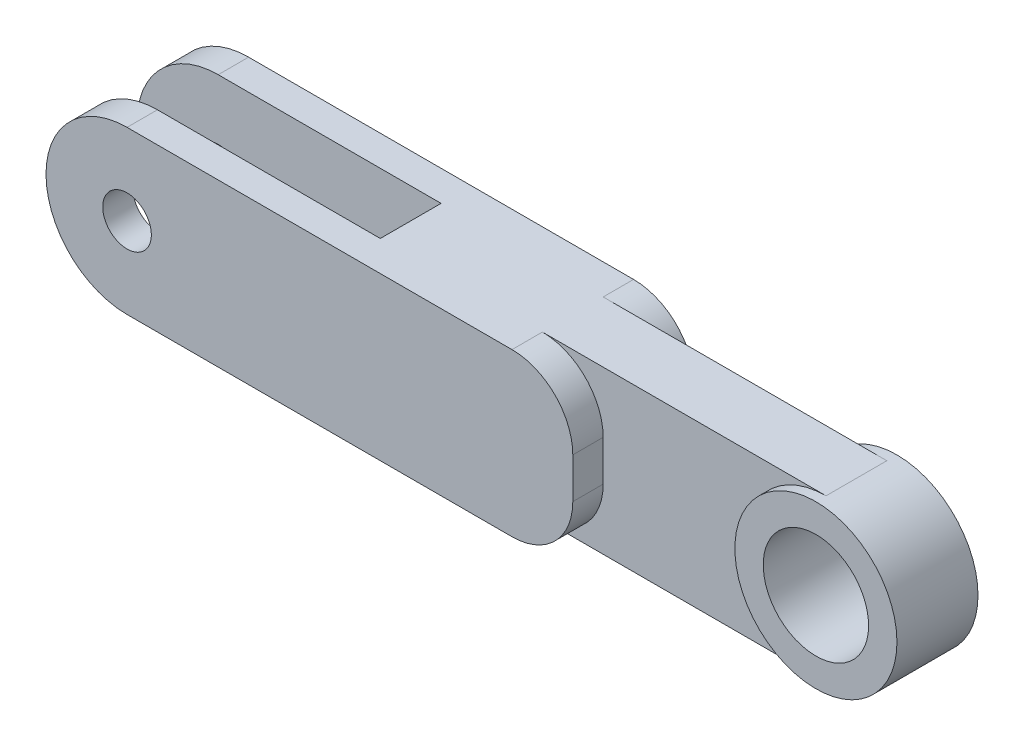
SolidWorks part; units mm, degrees
material "Vero PureWhite"
ref_plane "前视基准面" through (0, 0, 0) normal (0, 0, 1) x (1, 0, 0)
ref_plane "上视基准面" through (0, 0, 0) normal (0, 1, 0) x (1, 0, 0)
ref_plane "右视基准面" through (0, 0, 0) normal (1, 0, 0) x (0, 0, -1)
sketch "草图1" plane through (0, 0, 0) normal (0, 0, 1) x (1, 0, 0)
  line L0 (-21, 4) -> (12, 4)
  line L1 (-21, -4) -> (12, -4)
  circle A0 centre (-21, 0) radius 1.025
  circle A1 centre (12, 0) radius 2.6
  arc A2 (-21, 4) -> (-21, -4) centre (-21, 0) ccw
  arc A3 (12, -4) -> (12, 4) centre (12, 0) ccw
  dimension "D2" = 2.05
  dimension "D3" = 5.2
  dimension "D4" = 8
  dimension "D5" = 8
  dimension "D1" = 33
  dimension "D6" = 12
extrude "凸台-拉伸1" add sketch "草图1" along normal blind 3 and the other way blind 3
sketch "草图3" plane through (0, 0, 0) normal (0, 1, 0) x (1, 0, 0)
  line L0 (-25, 3) -> (-25, -3) construction
  line L1 (-25, 1.5) -> (-10, 1.5)
  line L2 (-25, 1.5) -> (-25, -1.5)
  line L3 (-25, -1.5) -> (-10, -1.5)
  line L4 (-10, 1.5) -> (-10, -1.5)
  line L5 (-25, 1.5) -> (-10, -1.5) construction
  line L6 (-25, -1.5) -> (-10, 1.5) construction
  line L8 (16, 3) -> (1, 3)
  line L9 (16, 3) -> (16, 1.5)
  line L10 (16, 1.5) -> (1, 1.5)
  line L11 (1, 3) -> (1, 1.5)
  line L12 (16, -3) -> (1, -3)
  line L13 (16, -3) -> (16, -1.5)
  line L14 (16, -1.5) -> (1, -1.5)
  line L15 (1, -3) -> (1, -1.5)
  point P0 (-17.5, 0)
  dimension "D1" = 3
  dimension "D2" = 15
  dimension "D3" = 1.5
  dimension "D4" = 1.5
  dimension "D5" = 15
  dimension "D6" = 15
extrude "切除-拉伸1" cut sketch "草图3" against normal blind 10 and the other way blind 10
fillet "圆角1" radius 3 4 edges at (1, -4, 2.25) (1, 4, 2.25) (1, -4, -2.25) (1, 4, -2.25)
sketch "草图4" plane through (0, 0, 1.5) normal (0, 0, 1) x (1, 0, 0)
  circle A0 centre (12, 0) radius 2.6
  circle A1 centre (12, 0) radius 4
  dimension "D1" = 5.2
extrude "凸台-拉伸2" add sketch "草图4" along normal blind 0.5
sketch "草图5" plane through (0, 0, -1.5) normal (0, 0, -1) x (-1, 0, 0)
  arc A0 (-12, 4) -> (-12, -4) centre (-12, 0) ccw construction
  circle A1 centre (-12, 0) radius 2.6 construction
  arc A2 (-12, -4) -> (-12, 4) centre (-12, 0) ccw construction
  arc A3 (-12, 4) -> (-12, -4) centre (-12, 0) ccw
  circle A4 centre (-12, 0) radius 2.6
  arc A5 (-12, -4) -> (-12, 4) centre (-12, 0) ccw
extrude "凸台-拉伸3" add sketch "草图5" along normal blind 0.5
sketch "草图6" plane through (0, 0, 3) normal (0, 0, 1) x (1, 0, 0)
  circle A0 centre (-21, 0) radius 1.2
  dimension "D1" = 2.4
extrude "切除-拉伸2" cut sketch "草图6" against normal blind 2
scale "缩放比例1" scale about origin uniform scaling yes scale factor 0.6
